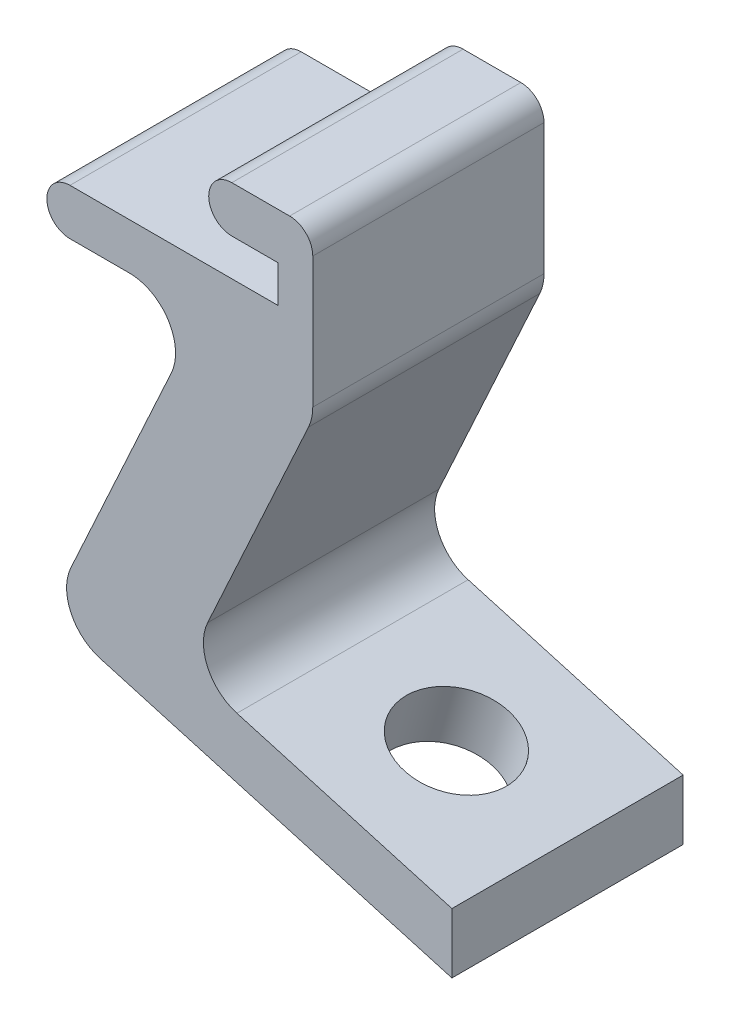
SolidWorks part; units mm, degrees
ref_plane "Front Plane" through (0, 0, 0) normal (0, 0, 1) x (1, 0, 0)
ref_plane "Top Plane" through (0, 0, 0) normal (0, 1, 0) x (1, 0, 0)
ref_plane "Right Plane" through (0, 0, 0) normal (1, 0, 0) x (0, 0, -1)
sketch "Sketch2" plane through (0, 0, 0) normal (0, 0, 1) x (1, 0, 0)
  line L1 (-1.5, 9.9701) -> (-1.5, 7.9701)
  line L2 (-1.5, 7.9701) -> (1.5, 7.9701)
  line L3 (1.5, 7.9701) -> (1.5, 6.3701)
  line L4 (1.5, 6.3701) -> (-8.5, 6.3701)
  line L5 (-8.5, 6.3701) -> (-8.5, 4.3701)
  line L7 (-1.5, 9.9701) -> (3, 9.9701)
  line L8 (3, 9.9701) -> (3, 3.3116)
  line L10 (-8.5, 4.3701) -> (-4.9335, 4.3701)
  line L11 (-3.1157, 1.5359) -> (-7.4636, -7.9383)
  line L12 (9.0172, -15.0576) -> (-6.1971, -10.695)
  line L13 (1.5, 7.1701) -> (-68.5, 7.1701) construction
  line L14 (-8.4343, -10.0535) -> (-68.5, 7.1701) construction
  line L15 (2.8177, 2.4774) -> (-1.5472, -7.034)
  line L16 (-0.2808, -9.7907) -> (9.0172, -12.4569)
  line L17 (9.0172, -12.4569) -> (9.0172, -15.0576)
  arc A0 (-7.4636, -7.9383) -> (-6.1971, -10.695) centre (-5.6459, -8.7724) ccw
  arc A1 (-0.2808, -9.7907) -> (-1.5472, -7.034) centre (0.2705, -7.8682) cw
  arc A2 (-4.9335, 4.3701) -> (-3.1157, 1.5359) centre (-4.9335, 2.3701) cw
  arc A3 (3, 3.3116) -> (2.8177, 2.4774) centre (1, 3.3116) cw
  point P3 (0, 0)
  point P22 (-2.518, -9.1492)
  dimension "D3" = 16
  dimension "D5" = 70
  dimension "D7" = 4.5
  dimension "D8" = 5
  dimension "D11" = 2
  dimension "D1" = 10
  dimension "D2" = 3
  dimension "D4" = 1.6
  dimension "D6" = 2
  dimension "D9" = 2.5
  dimension "D10" = 12
extrude "Boss-Extrude1" add sketch "Sketch2" along normal blind 10
fillet "Fillet1" radius 1 5 edges at (-8.5, 6.3701, 5) (-1.5, 7.9701, 5) (-1.5, 9.9701, 5) (3, 9.9701, 5) (-8.5, 4.3701, 5) tangent propagation no
sketch "Sketch3" plane through (-2.6155, -9.1213, 0) normal (0.2756, 0.9613, 0) x (0.9613, -0.2756, 0)
  line L0 (7.1015, -5) -> (7.1015, 0) construction
  line L1 (12.1015, 0) -> (2.4288, 0) construction
  line L2 (7.1015, -5) -> (12.1015, -5) construction
  line L3 (12.1015, -10) -> (12.1015, 0) construction
  circle A0 centre (7.1015, -5) radius 2.25
  dimension "D1" = 4.5
  dimension "D2" = 5
extrude "Cut-Extrude1" cut sketch "Sketch3" against normal blind 5
